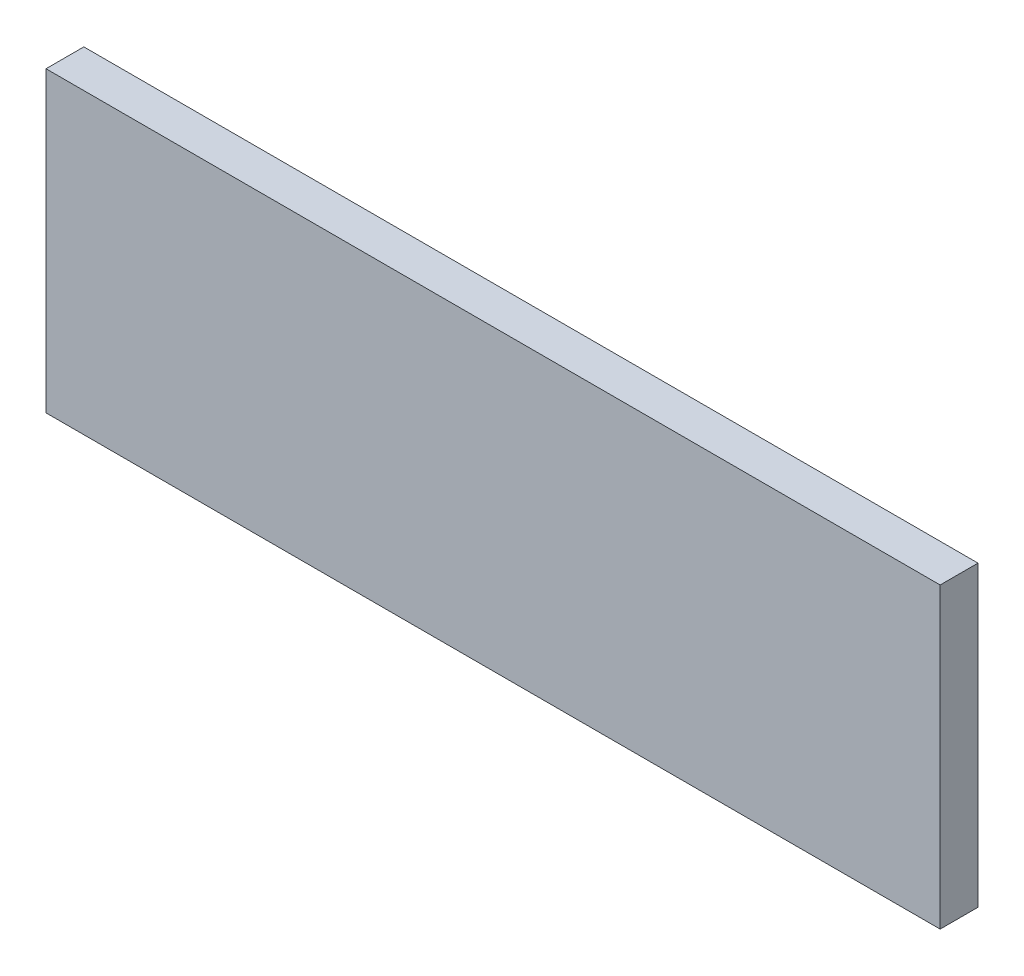
SolidWorks part; units mm, degrees
ref_plane "Front Plane" through (0, 0, 0) normal (0, 0, 1) x (1, 0, 0)
ref_plane "Top Plane" through (0, 0, 0) normal (0, 1, 0) x (1, 0, 0)
ref_plane "Right Plane" through (0, 0, 0) normal (1, 0, 0) x (0, 0, -1)
sketch "Sketch1" plane through (0, 0, 0) normal (0, 0, 1) x (1, 0, 0)
  line L1 (0, 0) -> (150, 0)
  line L2 (0, 0) -> (0, -50)
  line L3 (0, -50) -> (150, -50)
  line L4 (150, 0) -> (150, -50)
  dimension "D1" = 50
  dimension "D2" = 150
extrude "Boss-Extrude1" add sketch "Sketch1" along normal blind 6.35
